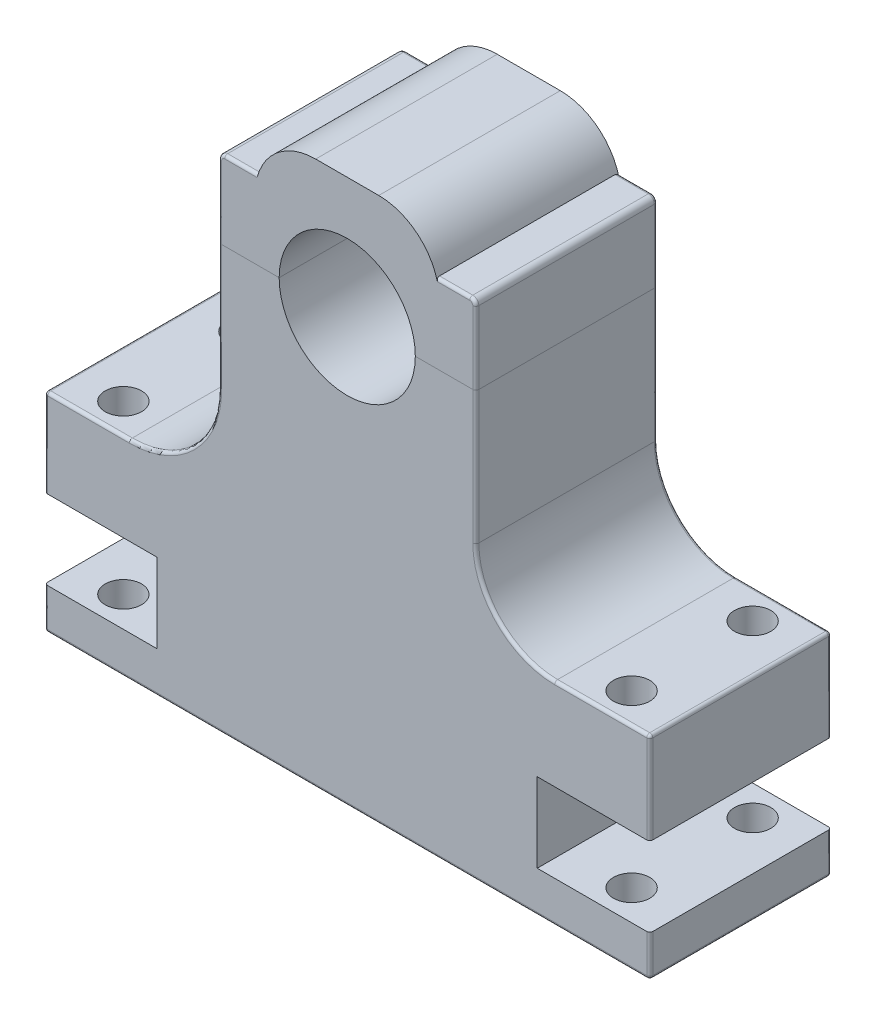
SolidWorks part; units mm, degrees
ref_plane "Plan de face" through (0, 0, 0) normal (0, 0, 1) x (1, 0, 0)
ref_plane "Plan de dessus" through (0, 0, 0) normal (0, 1, 0) x (1, 0, 0)
ref_plane "Plan de droite" through (0, 0, 0) normal (1, 0, 0) x (0, 0, -1)
sketch "Esquisse1" plane through (0, 0, 0) normal (0, 0, 1) x (1, 0, 0)
  line L0 (0, 0) -> (1000, 0)
  line L1 (1000, 0) -> (1000, 150)
  line L3 (0, 144.3329) -> (0, 0)
  line L4 (287.5, 374.9177) -> (287.5, 630)
  line L5 (352.5, 700) -> (647.5, 700)
  line L6 (712.5, 630) -> (712.5, 375)
  line L7 (0, 144.3329) -> (139.9789, 144.3329)
  line L8 (287.5, 291.854) -> (287.5, 374.9177)
  line L9 (1000, 150) -> (842.778, 150)
  line L10 (712.5, 375) -> (712.5, 280.278)
  line L11 (647.5, 700) -> (647.5, 630)
  line L12 (647.5, 630) -> (712.5, 630)
  line L13 (500, 500) -> (500, 0) construction
  line L16 (287.5, 630) -> (352.5, 630)
  line L17 (352.5, 700) -> (352.5, 630)
  circle A2 centre (500, 500) radius 112.5
  arc A3 (139.9789, 144.3329) -> (287.5, 291.854) centre (139.9789, 291.854) ccw
  arc A4 (842.778, 150) -> (712.5, 280.278) centre (842.778, 280.278) cw
  point P6 (320, 630)
  dimension "D1" = 225
  dimension "D2" = 500
  dimension "D3" = 65
  dimension "D4" = 700
  dimension "D5" = 65
  dimension "D6" = 287.5
  dimension "D7" = 1000
  dimension "D8" = 287.5
  dimension "D9" = 70
  dimension "D10" = 70
extrude "Boss.-Extru.1" add sketch "Esquisse1" against normal blind 300
sketch "Esquisse2" plane through (0, 144.3329, 0) normal (0, 1, 0) x (1, 0, 0)
  line L0 (139.9789, 300) -> (0, 300) construction
  line L1 (139.9789, 0) -> (0, 0) construction
  line L2 (0, 300) -> (0, 0) construction
  circle A0 centre (80, 250) radius 30
  circle A1 centre (80, 50) radius 30
  dimension "D1" = 60
  dimension "D2" = 60
  dimension "D3" = 50
  dimension "D4" = 50
  dimension "D5" = 80
  dimension "D6" = 80
extrude "Enlèv. mat.-Extru.1" cut sketch "Esquisse2" against normal blind 500
fillet "Congé3" radius 100 2 edges at (352.5, 700, -150) (647.5, 700, -150)
fillet "Congé4" radius 10 2 edges at (287.5, 630, -150) (712.5, 630, -150)
sketch "Esquisse3" plane through (0, 150, 0) normal (0, 1, 0) x (1, 0, 0)
  line L0 (1000, 300) -> (842.778, 300) construction
  line L1 (1000, 0) -> (842.778, 0) construction
  line L2 (1000, 300) -> (1000, 0) construction
  circle A0 centre (920, 250) radius 30
  circle A1 centre (920, 50) radius 30
  dimension "D1" = 60
  dimension "D2" = 60
  dimension "D3" = 50
  dimension "D4" = 50
  dimension "D5" = 80
  dimension "D6" = 80
extrude "Enlèv. mat.-Extru.2" cut sketch "Esquisse3" against normal through all
sketch "Esquisse6" plane through (0, 0, 0) normal (0, 0, 1) x (1, 0, 0)
  line L0 (0, 0) -> (0, -200)
  line L1 (0, -200) -> (1000, -200)
  line L2 (1000, -200) -> (1000, 0)
  line L3 (0, 0) -> (1000, 0) construction
  line L4 (0, 0) -> (1000, 0)
  dimension "D1" = 200
extrude "Boss.-Extru.2" add sketch "Esquisse6" against normal blind 300
sketch "Esquisse7" plane through (0, 0, 0) normal (0, 1, 0) x (1, 0, 0)
  circle A0 centre (80.6625, 253.0556) radius 33.1266
  circle A1 centre (80, 50) radius 30
  circle A3 centre (920, 250) radius 30
  circle A4 centre (920, 50) radius 30 construction
  circle A5 centre (920, 50) radius 30
extrude "Enlèv. mat.-Extru.4" cut sketch "Esquisse7" against normal blind 300
ref_plane "Plan2" through (500, 0, 0) normal (1, 0, 0) x (0, 0, -1)
sketch "Esquisse11" plane through (0, 630, 0) normal (0, 1, 0) x (1, 0, 0)
  line L0 (352.5, 300) -> (297.5, 300) construction
  line L1 (500, -165) -> (500, 165) construction
  circle A0 centre (325, 260) radius 20
  circle A1 centre (675, 260) radius 20
  circle A2 centre (325, 60) radius 20
  circle A3 centre (675, 60) radius 20
  dimension "D1" = 40
  dimension "D2" = 40
  dimension "D3" = 2
fillet "Congé6" radius 5 30 edges at (921.389, 150, 0) (675, 630, 0) (709.5711, 627.0711, 0) (712.5, 450.139, 0) (921.389, 150, -300) (675, 630, -300) (709.5711, 627.0711, -300) (712.5, 450.139, -300) (325, 630, -300) (290.4289, 627.0711, -300) (287.5, 455.927, -300) (244.2921, 187.5409, -300) (325, 630, 0) (290.4289, 627.0711, 0) (69.9895, 144.3329, 0) (244.2921, 187.5409, 0) (1000, -200, -150) (500, -200, -300) (0, -200, -150) (500, -200, 0) (750.6576, 188.1576, 0) (1000, 150, -150) (1000, -25, 0) (1000, -25, -300) (750.6576, 188.1576, -300) (69.9895, 144.3329, -300) (0, -27.8335, -300) (0, 144.3329, -150) (0, -27.8335, 0) (287.5, 455.927, 0)
ref_plane "Plan1" through (0, 500, 0) normal (0, -1, 0) x (-1, 0, 0)
split "Fractionner1" trim tools "Plan1" bodies to split 107 resulting bodies 108 109
sketch "Esquisse12" plane through (0, 0, -300) normal (0, 0, -1) x (-1, 0, 0)
  line L0 (0, 139.3329) -> (0, -195) construction
  line L1 (-186, -1) -> (264.7288, -1)
  line L2 (-186, -1) -> (-186, -132)
  line L3 (-186, -132) -> (264.7288, -132)
  line L4 (264.7288, -1) -> (264.7288, -132)
  line L5 (39.3644, -132) -> (39.3644, -1) construction
  line L6 (-186, -66.5) -> (264.7288, -66.5) construction
  line L7 (-995, -195) -> (-5, -195) construction
  line L8 (-500, 165) -> (-500, -165) construction
  line L9 (-814, -132) -> (-1264.7288, -132)
  line L10 (-1264.7288, -1) -> (-1264.7288, -132)
  line L11 (-814, -1) -> (-1264.7288, -1)
  line L12 (-814, -1) -> (-814, -132)
  point P72 (39.3644, -66.5)
  dimension "D1" = 186
  dimension "D2" = 131
  dimension "D3" = 63
extrude "Enlèv. mat.-Extru.5" cut sketch "Esquisse12" against normal through all
